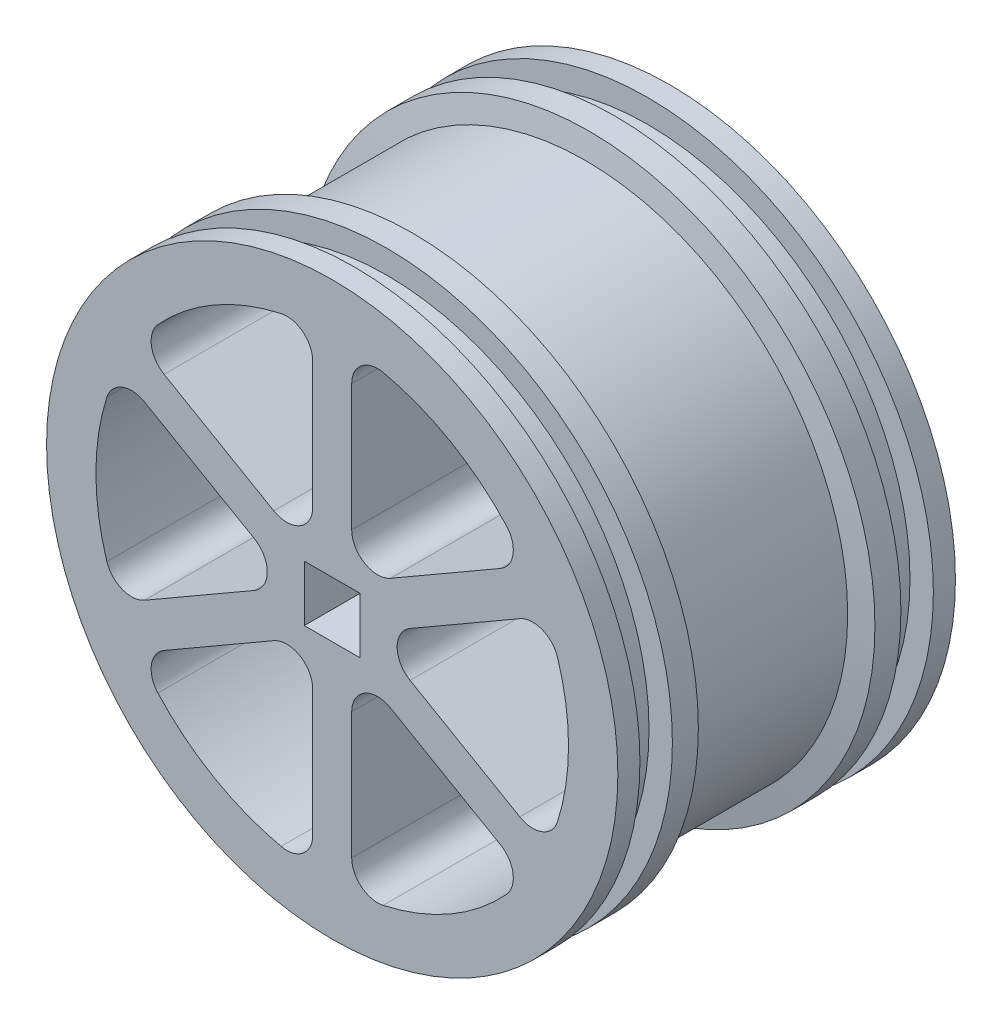
SolidWorks part; units mm, degrees
ref_plane "Front Plane" through (0, 0, 0) normal (0, 0, 1) x (1, 0, 0)
ref_plane "Top Plane" through (0, 0, 0) normal (0, 1, 0) x (1, 0, 0)
ref_plane "Right Plane" through (0, 0, 0) normal (1, 0, 0) x (0, 0, -1)
sketch "Sketch1" plane through (0, 0, 0) normal (1, 0, 0) x (0, 0, -1)
  line L1 (0, 22) -> (1.7, 22)
  line L2 (1.7, 22) -> (1.7, 20.2)
  line L3 (1.7, 20.2) -> (4.2, 20.2)
  line L4 (4.2, 20.2) -> (4.2, 22)
  line L5 (4.2, 22) -> (6.2, 22)
  line L6 (6.2, 22) -> (6.5, 20.2)
  line L7 (19.8, 22) -> (19.5, 20.2)
  line L8 (19.5, 20.2) -> (6.5, 20.2)
  line L10 (0, 18.2) -> (26, 18.2)
  line L11 (19.8, 22) -> (21.8, 22)
  line L12 (21.8, 22) -> (21.8, 20.2)
  line L13 (21.8, 20.2) -> (24.3, 20.2)
  line L14 (24.3, 20.2) -> (24.3, 22)
  line L15 (24.3, 22) -> (26, 22)
  line L18 (-0.3222, 0) -> (27.2819, 0) construction
  line L19 (0, 0) -> (0, 18.2) construction
  line L20 (0, 22) -> (0, 1028.7814) construction
  line L21 (0, 22) -> (0, 18.2)
  line L22 (26, 22) -> (26, 18.2)
  dimension "D1" = 22
  dimension "D2" = 1.7
  dimension "D3" = 2
  dimension "D4" = 0.3
  dimension "D5" = 2.3
  dimension "D6" = 3.8
  dimension "D7" = 1.8
  dimension "D8" = 2.5
  dimension "D9" = 26
revolve "Revolve1" add sketch "Sketch1" angle 360 about L18
sketch "Sketch2" plane through (0, 0, 0) normal (0, 0, 1) x (1, 0, 0)
  line L0 (0, 0) -> (0, 18.2) construction
  line L1 (-1.5, 18.2) -> (-1.5, 0)
  line L2 (-1.5, 18.2) -> (1.5, 18.2)
  line L3 (-1.5, 0) -> (1.5, 0)
  line L4 (1.5, 18.2) -> (1.5, 0)
  line L5 (-1.5, 18.2) -> (1.5, 0) construction
  line L6 (-1.5, 0) -> (1.5, 18.2) construction
  circle A0 centre (0, 0) radius 18.2 construction
  point P6 (0, 9.1)
  dimension "D1" = 18.2
  dimension "D2" = 3
extrude "Boss-Extrude1" add sketch "Sketch2" against normal blind 24
pattern_circular "CirPattern1" count 6 over 360 about axis through (0, 0, 0.3222) along (0, 0, 1) of "Boss-Extrude1" reverse direction yes
sketch "Sketch3" plane through (0, 0, 0) normal (0, 0, 1) x (1, 0, 0)
  line L1 (-2.15, -2.15) -> (2.15, -2.15)
  line L2 (-2.15, -2.15) -> (-2.15, 2.15)
  line L3 (-2.15, 2.15) -> (2.15, 2.15)
  line L4 (2.15, -2.15) -> (2.15, 2.15)
  line L5 (-2.15, -2.15) -> (2.15, 2.15) construction
  line L6 (-2.15, 2.15) -> (2.15, -2.15) construction
  point P0 (0, 0)
  dimension "D1" = 4.3
extrude "Cut-Extrude1" cut sketch "Sketch3" against normal through all both and the other way through all
fillet "Fillet1" radius 2 18 edges at (-14.958, 10.3681, -12) (16.458, -7.77, -12) (-1.5, 18.1381, -12) (-1.5, 2.5981, -12) (1.5, 18.1381, -12) (14.958, 10.3681, -12) (1.5, 2.5981, -12) (16.458, 7.77, -12) (3, 0, -12) (1.5, -2.5981, -12) (14.958, -10.3681, -12) (1.5, -18.1381, -12) (-1.5, -2.5981, -12) (-1.5, -18.1381, -12) (-14.958, -10.3681, -12) (-16.458, -7.77, -12) (-16.458, 7.77, -12) (-3, 0, -12)
fillet "Fillet2" radius 2 1 edges at (18.2, 0, -26)
sketch "Sketch4" plane through (0, 0, 0) normal (1, 0, 0) x (0, 0, -1)
  line L0 (0, 0) -> (26, 0) construction
  line L1 (26, -22) -> (26, 22) construction
ref_axis "Axis1" through (0, 0, 0) along (0, 0, -1)
